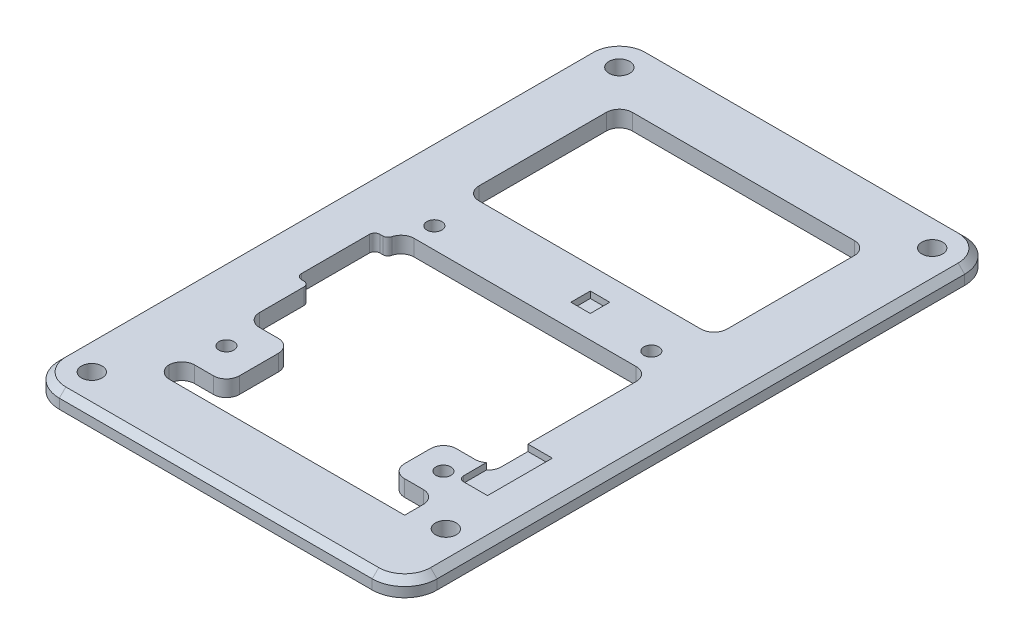
SolidWorks part; units mm, degrees
ref_plane "Front Plane" through (0, 0, 0) normal (0, 0, 1) x (1, 0, 0)
ref_plane "Top Plane" through (0, 0, 0) normal (0, 1, 0) x (1, 0, 0)
ref_plane "Right Plane" through (0, 0, 0) normal (1, 0, 0) x (0, 0, -1)
sketch "Sketch1" plane through (0, 0, 0) normal (0, 1, 0) x (1, 0, 0)
  line L4 (26.75, 55.875) -> (-26.75, 55.875)
  line L5 (26.75, -45.825) -> (26.75, 55.875)
  line L6 (-26.75, -45.825) -> (26.75, -45.825)
  line L7 (-26.75, 55.875) -> (-26.75, -45.825)
  line L8 (26.75, 55.875) -> (-26.75, 55.875)
  line L9 (26.75, -45.825) -> (26.75, 55.875)
  line L10 (-26.75, -45.825) -> (26.75, -45.825)
  line L11 (-26.75, 55.875) -> (-26.75, -45.825)
  line L12 (3.325, 28.475) -> (-2.675, 28.475)
  line L13 (3.325, 24.185) -> (3.325, 28.475)
  line L14 (-2.675, 24.185) -> (3.325, 24.185)
  line L15 (-2.675, 28.475) -> (-2.675, 24.185)
  line L16 (3.325, 28.475) -> (-2.675, 28.475)
  line L17 (3.325, 24.185) -> (3.325, 28.475)
  line L18 (-2.675, 24.185) -> (3.325, 24.185)
  line L19 (-2.675, 28.475) -> (-2.675, 24.185)
  line L20 (-2.675, 4.275) -> (3.325, 4.275)
  line L21 (3.325, 4.275) -> (3.325, 8.565)
  line L22 (3.325, 8.565) -> (-2.675, 8.565)
  line L23 (-2.675, 8.565) -> (-2.675, 4.275)
  line L24 (-2.675, 4.275) -> (3.325, 4.275)
  line L25 (3.325, 4.275) -> (3.325, 8.565)
  line L26 (3.325, 8.565) -> (-2.675, 8.565)
  line L27 (-2.675, 8.565) -> (-2.675, 4.275)
  circle A1 centre (24.125, -34.325) radius 1.5
  circle A2 centre (24.125, -34.325) radius 1.5
  circle A3 centre (-24.125, -40.675) radius 1.5
  circle A4 centre (-24.125, -40.675) radius 1.5
  circle A5 centre (24.125, 40.675) radius 1.5
  circle A6 centre (24.125, 40.675) radius 1.5
  circle A7 centre (-24.125, 40.675) radius 1.5
  circle A8 centre (-24.125, 40.675) radius 1.5
  dimension "D1" = 0
  dimension "D2" = 0
  dimension "D3" = 0
  dimension "D4" = 0
  dimension "D5" = 0
  dimension "D6" = 0
  dimension "D7" = 0
sketch "Sketch2" plane through (0, 0, 0) normal (0, 1, 0) x (1, 0, 0)
  line L0 (-24.125, 40.675) -> (24.125, 40.675) construction
  line L1 (24.125, 40.675) -> (24.125, -40.675) construction
  line L2 (24.125, -40.675) -> (-24.125, -40.675) construction
  line L3 (-24.125, -40.675) -> (-24.125, 40.675) construction
  line L4 (-29.125, -45.675) -> (-29.125, 45.675)
  line L5 (-29.125, 45.675) -> (29.125, 45.675)
  line L6 (29.125, 45.675) -> (29.125, -45.675)
  line L7 (29.125, -45.675) -> (-29.125, -45.675)
  line L8 (-19.125, -35.675) -> (-19.125, 35.675)
  line L9 (-19.125, 35.675) -> (19.125, 35.675)
  line L10 (19.125, 35.675) -> (19.125, -35.675)
  line L11 (19.125, -35.675) -> (-19.125, -35.675)
  circle A0 centre (24.125, 40.675) radius 1.5 construction
  circle A1 centre (24.125, -34.325) radius 1.5 construction
  circle A2 centre (-24.125, -40.675) radius 1.5 construction
  circle A3 centre (-24.125, 40.675) radius 1.5 construction
  circle A4 centre (24.125, 40.675) radius 1.5
  circle A5 centre (24.125, -34.325) radius 1.5
  circle A6 centre (-24.125, -40.675) radius 1.5
  circle A7 centre (-24.125, 40.675) radius 1.5
  dimension "D1" = 5
  dimension "D2" = 5
sketch "Sketch3" plane through (0, 0, 0) normal (0, 1, 0) x (1, 0, 0)
  line L0 (29.125, -45.675) -> (-29.125, -45.675) construction
  line L1 (-23.5, 9.325) -> (23.5, 9.325)
  line L2 (-23.5, 9.325) -> (-23.5, -30.675)
  line L3 (-23.5, -30.675) -> (23.5, -30.675)
  line L4 (23.5, 9.325) -> (23.5, -30.675)
  line L5 (-23.5, 9.325) -> (23.5, -30.675)
  line L6 (-23.5, -30.675) -> (23.5, 9.325)
  line L7 (-20.5, -0.675) -> (-14.9, -0.675)
  line L8 (-20.5, -0.675) -> (-20.5, -11.575)
  line L9 (-20.5, -11.575) -> (-14.9, -11.575)
  line L10 (-14.9, -0.675) -> (-14.9, -11.575)
  line L11 (5.2, -6.775) -> (16.8, -6.775)
  line L12 (5.2, -6.775) -> (5.2, -21.775)
  line L13 (5.2, -21.775) -> (16.8, -21.775)
  line L14 (16.8, -6.775) -> (16.8, -21.775)
  line L16 (18.4, -16.675) -> (22.9, -16.675)
  line L18 (18.4, -16.675) -> (18.4, -26.675)
  line L19 (18.4, -26.675) -> (22.9, -26.675)
  line L20 (22.9, -16.675) -> (22.9, -26.675)
  line L21 (3.5, 8.575) -> (6.5, 8.575)
  line L22 (3.5, 8.575) -> (3.5, 5.575)
  line L23 (3.5, 5.575) -> (6.5, 5.575)
  line L24 (6.5, 8.575) -> (6.5, 5.575)
  circle A0 centre (-17.23, -26.805) radius 1.27
  circle A1 centre (16.23, -26.805) radius 1.27
  circle A2 centre (-17.23, 5.255) radius 1.27
  circle A3 centre (16.23, 5.255) radius 1.27
  point P0 (0, -10.675)
  point P21 (16.23, 6.525)
  point P23 (-18.5, 5.255)
  point P24 (17.5, 5.255)
  point P27 (16.23, -28.075)
  dimension "D15" = 2.54
  dimension "D1" = 47
  dimension "D2" = 40
  dimension "D3" = 10.9
  dimension "D4" = 5.6
  dimension "D5" = 3
  dimension "D6" = 10
  dimension "D7" = 11.6
  dimension "D8" = 15
  dimension "D9" = 8.9
  dimension "D10" = 6.7
  dimension "D11" = 5
  dimension "D12" = 6
  dimension "D13" = 2.8
  dimension "D14" = 2.6
  dimension "D16" = 15
  dimension "D17" = 10
  dimension "D18" = 4
  dimension "D19" = 0.6
  dimension "D20" = 4.5
  dimension "D21" = 3
  dimension "D22" = 0.75
  dimension "D23" = 17
sketch "Sketch5" plane through (0, 0, 0) normal (0, 1, 0) x (1, 0, 0)
  line L0 (-19.125, 2.025) -> (19.125, 2.025)
  line L1 (-23.5, 9.325) -> (23.5, 9.325) construction
  line L2 (-19.125, 12.025) -> (19.125, 12.025)
  line L3 (-19.125, 2.025) -> (-19.125, -21.805)
  line L4 (-19.125, 35.675) -> (-19.125, -35.675)
  line L5 (19.125, 35.675) -> (-19.125, 35.675)
  line L6 (19.125, -35.675) -> (19.125, 35.675)
  line L7 (-19.125, -35.675) -> (19.125, -35.675)
  line L8 (-19.125, 35.675) -> (-19.125, 12.025)
  line L9 (19.125, 35.675) -> (-19.125, 35.675)
  line L10 (19.125, -35.675) -> (19.125, -30.805)
  line L11 (-19.125, -35.675) -> (19.125, -35.675)
  line L12 (29.125, -45.675) -> (29.125, 45.675)
  line L13 (29.125, 45.675) -> (-29.125, 45.675)
  line L14 (-29.125, 45.675) -> (-29.125, -45.675)
  line L15 (-29.125, -45.675) -> (29.125, -45.675)
  line L16 (29.125, -45.675) -> (29.125, 45.675)
  line L17 (29.125, 45.675) -> (-29.125, 45.675)
  line L18 (-29.125, 45.675) -> (-29.125, -45.675)
  line L19 (-29.125, -45.675) -> (29.125, -45.675)
  line L20 (19.125, 12.025) -> (19.125, 35.675)
  line L21 (-19.125, -31.805) -> (-19.125, -35.675)
  line L22 (-19.125, -21.805) -> (-12.23, -21.805)
  line L28 (-19.125, -31.805) -> (-12.23, -31.805)
  line L29 (-12.23, -21.805) -> (-12.23, -31.805)
  line L30 (19.125, -22.805) -> (12.23, -22.805)
  line L32 (19.125, -30.805) -> (12.23, -30.805)
  line L33 (12.23, -22.805) -> (12.23, -30.805)
  line L34 (19.125, -22.805) -> (19.125, 2.025)
  line L35 (16.23, -26.805) -> (16.23, -30.805) construction
  line L36 (16.23, -26.805) -> (12.23, -26.805) construction
  line L37 (-17.23, -26.805) -> (-12.23, -26.805) construction
  line L39 (-17.23, -26.805) -> (-17.23, -31.805) construction
  circle A0 centre (-17.23, 5.255) radius 1.15
  circle A2 centre (-24.125, 40.675) radius 1.6
  circle A4 centre (-24.125, -40.675) radius 1.6
  circle A6 centre (24.125, -34.325) radius 1.6
  circle A8 centre (24.125, 40.675) radius 1.6
  circle A9 centre (-17.23, -26.805) radius 1.27
  circle A10 centre (-17.23, -26.805) radius 1.27 construction
  circle A11 centre (16.23, 5.255) radius 1.27
  circle A12 centre (16.23, 5.255) radius 1.27 construction
  circle A13 centre (-17.23, 5.255) radius 1.27
  circle A14 centre (-17.23, 5.255) radius 1.27 construction
  circle A15 centre (16.23, -26.805) radius 1.27
  circle A16 centre (16.23, -26.805) radius 1.27 construction
  circle A17 centre (16.23, 5.255) radius 1.15
  circle A18 centre (16.23, -26.805) radius 1.15
  circle A19 centre (-17.23, -26.805) radius 1.15
  point P46 (12.23, -26.805)
  point P47 (-12.23, -26.805)
  dimension "D14" = 2.3
  dimension "D2" = 3.2
  dimension "D11" = 7.3
  dimension "D12" = 10
  dimension "D3" = 10
  dimension "D4" = 8
  dimension "D5" = 0
  dimension "D6" = 0
  dimension "D7" = 0
  dimension "D8" = 0
  dimension "D9" = 0
  dimension "D10" = 0
extrude "Boss-Extrude1" add sketch "Sketch5" along normal blind 2.5
sketch "Sketch8" plane through (0, 2.5, 0) normal (0, 1, 0) x (1, 0, 0)
  line L0 (18.4, -16.675) -> (22.9, -16.675) construction
  line L1 (18.4, -16.675) -> (18.4, -26.675) construction
  line L2 (22.9, -16.675) -> (22.9, -26.675) construction
  line L3 (18.4, -26.675) -> (22.9, -26.675) construction
  line L4 (18.4, -16.675) -> (22.9, -16.675)
  line L5 (18.4, -16.675) -> (18.4, -26.675)
  line L6 (22.9, -16.675) -> (22.9, -26.675)
  line L7 (18.4, -26.675) -> (22.9, -26.675)
  line L8 (3.5, 8.575) -> (3.5, 5.575) construction
  line L9 (3.5, 8.575) -> (6.5, 8.575) construction
  line L10 (6.5, 8.575) -> (6.5, 5.575) construction
  line L11 (3.5, 5.575) -> (6.5, 5.575) construction
  line L12 (3.5, 8.575) -> (3.5, 5.575)
  line L13 (3.5, 8.575) -> (6.5, 8.575)
  line L14 (6.5, 8.575) -> (6.5, 5.575)
  line L15 (3.5, 5.575) -> (6.5, 5.575)
extrude "Cut-Extrude1" cut sketch "Sketch8" against normal blind 1
fillet "Fillet1" radius 2 15 edges at (19.125, 1.25, -12.025) (19.125, 1.25, -35.675) (-19.125, 1.25, -12.025) (-19.125, 1.25, -35.675) (19.125, 1.25, -2.025) (-19.125, 1.25, -2.025) (-19.125, 1.25, 21.805) (19.125, 0.75, 22.805) (19.125, 1.25, 30.805) (-19.125, 1.25, 31.805) (-19.125, 1.25, 35.675) (12.23, 1.25, 30.805) (12.23, 1.25, 22.805) (-12.23, 1.25, 31.805) (-12.23, 1.25, 21.805)
fillet "Fillet2" radius 5 4 edges at (29.125, 1.25, 45.675) (-29.125, 1.25, 45.675) (-29.125, 1.25, -45.675) (29.125, 1.25, -45.675)
sketch "Sketch9" plane through (0, 0, 0) normal (0, -1, 0) x (1, 0, 0)
  line L0 (-14.9, 0.675) -> (-14.9, 11.575) construction
  line L1 (-20.5, 11.575) -> (-14.9, 11.575) construction
  line L2 (-20.5, 0.675) -> (-14.9, 0.675) construction
  line L3 (-20.5, 0.675) -> (-20.5, 11.575) construction
  line L4 (-14.9, 0.675) -> (-14.9, 11.575) construction
  line L5 (-20.5, 11.575) -> (-14.9, 11.575) construction
  line L6 (-20.5, 0.675) -> (-14.9, 0.675) construction
  line L7 (-20.5, 0.675) -> (-20.5, 11.575) construction
  line L8 (-14.3, 0.075) -> (-14.3, 12.175)
  line L9 (-21.1, 12.175) -> (-14.3, 12.175)
  line L10 (-21.1, 0.075) -> (-21.1, 12.175)
  line L11 (-21.1, 0.075) -> (-14.3, 0.075)
  dimension "D1" = 0.6
extrude "Cut-Extrude2" cut sketch "Sketch9" against normal through all
sketch "Sketch10" plane through (0, 0, 0) normal (0, 1, 0) x (1, 0, 0)
  line L0 (3.325, 4.275) -> (3.325, 8.565) construction
  line L1 (-2.675, 4.275) -> (3.325, 4.275) construction
  line L2 (3.325, 8.565) -> (-2.675, 8.565) construction
  line L3 (-2.675, 8.565) -> (-2.675, 4.275) construction
  line L4 (3.325, 4.275) -> (3.325, 8.565) construction
  line L5 (-2.675, 4.275) -> (3.325, 4.275) construction
  line L6 (3.325, 8.565) -> (-2.675, 8.565) construction
  line L7 (-2.675, 8.565) -> (-2.675, 4.275) construction
  line L8 (3.925, 3.675) -> (3.925, 9.165)
  line L9 (3.925, 9.165) -> (-3.275, 9.165)
  line L10 (-3.275, 9.165) -> (-3.275, 3.675)
  line L11 (-3.275, 3.675) -> (3.925, 3.675)
  dimension "D1" = 0.6
extrude "Cut-Extrude3" cut sketch "Sketch10" along normal blind 1
fillet "Fillet3" radius 0.8 9 edges at (-19.125, 1.25, 12.175) (-21.1, 1.25, 12.175) (-19.125, 1.25, 0.075) (-21.1, 1.25, 0.075) (3.925, 0.5, -3.675) (3.925, 0.5, -9.165) (-3.275, 0.5, -9.165) (-3.275, 0.5, -3.675) (18.4, 2, 26.675)
chamfer "Chamfer3" distance 1 angle 45 8 edges at (0, 2.5, 45.675) (27.6605, 2.5, 44.2105) (-27.6605, 2.5, 44.2105) (29.125, 2.5, 0) (-29.125, 2.5, 0) (27.6605, 2.5, -44.2105) (-27.6605, 2.5, -44.2105) (0, 2.5, -45.675)
